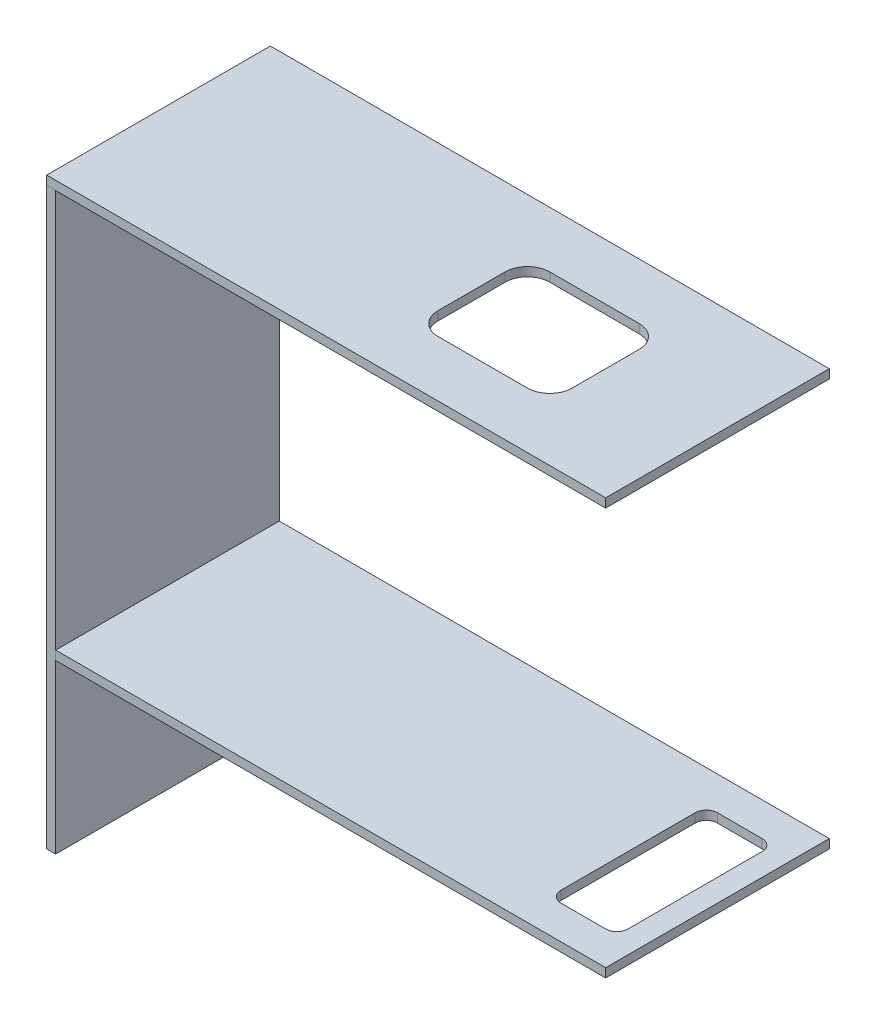
SolidWorks part; units mm, degrees
ref_plane "Front Plane" through (0, 0, 0) normal (0, 0, 1) x (1, 0, 0)
ref_plane "Top Plane" through (0, 0, 0) normal (0, 1, 0) x (1, 0, 0)
ref_plane "Right Plane" through (0, 0, 0) normal (1, 0, 0) x (0, 0, -1)
sketch "Sketch1" plane through (0, 0, 0) normal (0, 0, 1) x (1, 0, 0)
  line L0 (-122, -53.5) -> (124, -53.5)
  line L1 (124, 132.5) -> (-126, 132.5)
  line L2 (124, 132.5) -> (124, 128.5)
  line L3 (124, 128.5) -> (-126, 128.5)
  line L4 (-126, 132.5) -> (-126, 128.5)
  line L5 (124, 132.5) -> (-126, 128.5) construction
  line L6 (124, 128.5) -> (-126, 132.5) construction
  line L7 (-126, 128.5) -> (-122, 128.5)
  line L8 (-126, 128.5) -> (-126, -128.5)
  line L9 (-126, -128.5) -> (-122, -128.5)
  line L10 (-122, 128.5) -> (-122, -128.5)
  line L14 (124, -53.5) -> (124, -49.5)
  line L15 (124, -49.5) -> (-122, -49.5)
  line L16 (-122, -49.5) -> (-122, -53.5)
  point P0 (30.25, 130)
  dimension "D1" = 4
  dimension "D2" = 250
  dimension "D3" = 124
  dimension "D4" = 1.5
  dimension "D5" = 4
  dimension "D6" = 257
  dimension "D7" = 4
  dimension "D8" = 246
  dimension "D9" = 75
  dimension "D10" = 128.5
extrude "Boss-Extrude1" add sketch "Sketch1" along normal blind 100 contours L1 L4 L3 L2 region at (-1, 130.5, 0)
extrude "Boss-Extrude2" add sketch "Sketch1<3>" along normal blind 100 separate body contours L10 L3 L8 L9 region at (-124, 0, 0)
sketch "Sketch1<3>" plane through (0, 0, 0) normal (0, 0, 1) x (1, 0, 0) same geometry as "Sketch1"
extrude "Boss-Extrude3" add sketch "Sketch1<4>" along normal blind 100 separate body contours L14 L15 L10 L0 region at (1, -51.5, 0)
sketch "Sketch1<4>" plane through (0, 0, 0) normal (0, 0, 1) x (1, 0, 0) same geometry as "Sketch1"
sketch "Sketch2" plane through (0, -49.5, 0) normal (0, 1, 0) x (1, 0, 0)
  line L0 (124, 0) -> (-122, 0) construction
  line L2 (124, -100) -> (124, 0) construction
  line L3 (89, -15) -> (109, -15)
  line L4 (84, -20) -> (84, -80)
  line L5 (89, -85) -> (109, -85)
  line L6 (114, -20) -> (114, -80)
  line L7 (124, -100) -> (-122, -100) construction
  arc A1 (89, -85) -> (84, -80) centre (89, -80) cw
  arc A2 (109, -85) -> (114, -80) centre (109, -80) ccw
  arc A3 (114, -20) -> (109, -15) centre (109, -20) ccw
  arc A4 (84, -20) -> (89, -15) centre (89, -20) cw
  point P10 (84, -85)
  point P15 (114, -15)
  point P18 (84, -15)
  dimension "D1" = 30
  dimension "D2" = 15
  dimension "D3" = 10
  dimension "D5" = 5
  dimension "D4" = 15
extrude "Cut-Extrude1" cut sketch "Sketch2" along direction (0, 1, 0) on the side against the normal up to surface (4 mm away) from surface contours A4 L4 A1 L5 A2 L6 A3 L3 up to face at (1, -53.5, 50) starting at face at (1, -49.5, 50)
sketch "Sketch3" plane through (0, 132.5, 0) normal (0, 1, 0) x (1, 0, 0)
  line L7 (14, -65) -> (14, -35)
  line L8 (24, -25) -> (64, -25)
  line L9 (74, -65) -> (74, -35)
  line L10 (24, -75) -> (64, -75)
  line L11 (124, -100) -> (124, 0) construction
  arc A4 (74, -35) -> (64, -25) centre (64, -35) ccw
  arc A5 (74, -65) -> (64, -75) centre (64, -65) cw
  arc A6 (24, -75) -> (14, -65) centre (24, -65) cw
  arc A7 (24, -25) -> (14, -35) centre (24, -35) ccw
  point P0 (0, 0)
  dimension "D1" = 40
  dimension "D6" = 50
  dimension "D7" = 60
  dimension "D8" = 50
extrude "Cut-Extrude2" cut sketch "Sketch3" along normal up to surface (-4 mm away) from surface contours L8 A7 L7 A6 L10 A5 L9 A4 up to face at (-1, 128.5, 50) starting at face at (-1, 132.5, 50)
